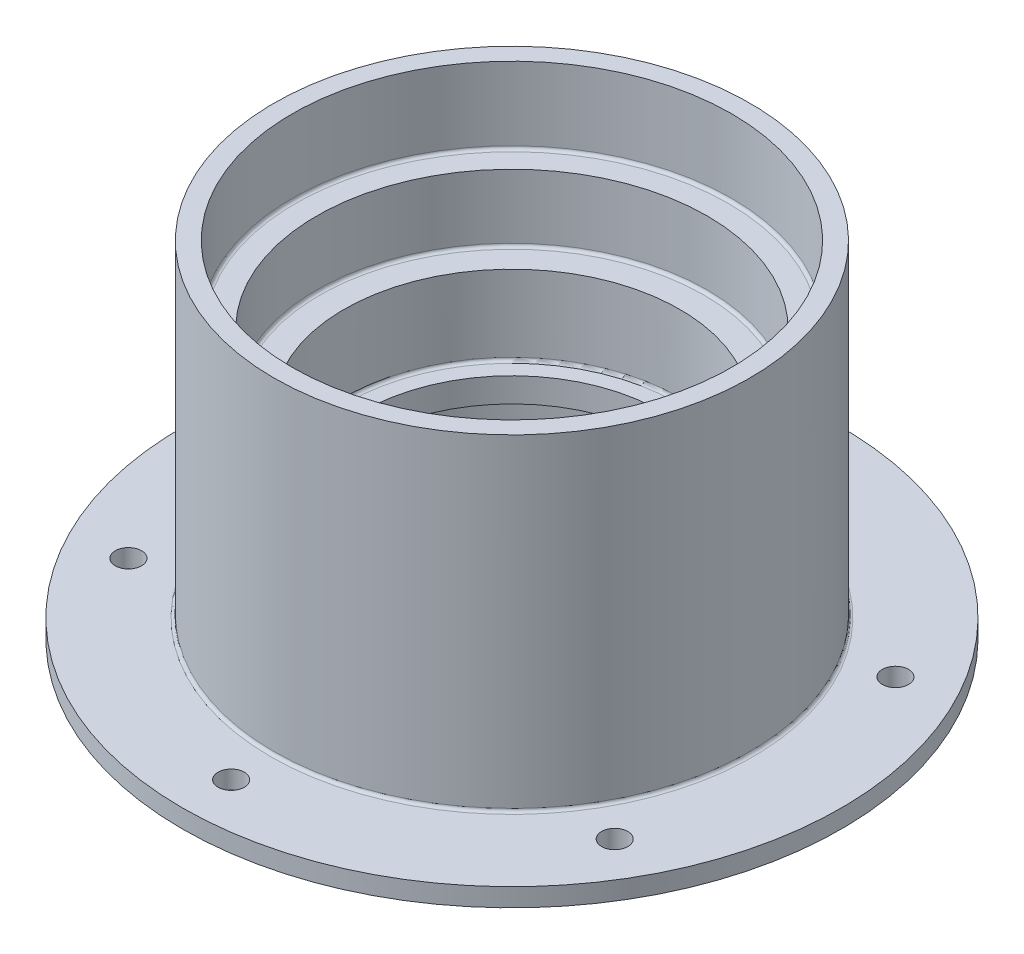
SolidWorks part; units mm, degrees
material "1060 Alloy"
ref_plane "Front" through (0, 0, 0) normal (0, 0, 1) x (1, 0, 0)
ref_plane "Top" through (0, 0, 0) normal (0, 1, 0) x (1, 0, 0)
ref_plane "Right" through (0, 0, 0) normal (1, 0, 0) x (0, 0, -1)
sketch "Sketch1" plane through (0, 0, 0) normal (0, 0, 1) x (1, 0, 0)
  line L0 (0, 0) -> (-39, 0)
  line L1 (-39, 0) -> (-39, -56.5)
  line L2 (-36, 0) -> (-36, -2)
  line L3 (-32, -15.5) -> (-32, -26.5)
  line L4 (-27.5, -26.5) -> (-27.5, -39.5)
  line L5 (-24.5, -39.5) -> (-24.5, -43.5)
  line L6 (-36, -3) -> (-37, -3)
  line L7 (-36, -15.5) -> (-32, -15.5)
  line L8 (-32, -26.5) -> (-27.5, -26.5)
  line L9 (-27.5, -39.5) -> (-24.5, -39.5)
  line L10 (-24.5, -43.5) -> (-32, -43.5)
  line L11 (-32, -59.5) -> (-54, -59.5)
  line L12 (-54, -59.5) -> (-54, -56.5)
  line L13 (-54, -56.5) -> (-39, -56.5)
  line L14 (0, 0) -> (0, -7.967)
  line L15 (-27.5, 0) -> (-27.5, -59.5) construction
  line L16 (-24.5, 0) -> (-24.5, -59.5) construction
  line L17 (-32, 0) -> (-32, -59.5) construction
  line L18 (-32, -43.5) -> (-32, -59.5)
  line L19 (-36, 0) -> (-36, -59.5) construction
  line L20 (-39, 0) -> (-39, -59.5) construction
  line L21 (-37, -3) -> (-37, -2)
  line L22 (-37, -2) -> (-36, -2)
  line L23 (-36, -3) -> (-36, -15.5)
  line L24 (-36, -0.5) -> (-39, -0.5)
  line L25 (-37, -3) -> (-39, -3)
  dimension "D2" = 3
  dimension "D3" = 4
  dimension "D4" = 4.5
  dimension "D5" = 3
  dimension "D6" = 3
  dimension "D7" = 12.5
  dimension "D8" = 11
  dimension "D9" = 13
  dimension "D10" = 4
  dimension "D11" = 16
  dimension "D12" = 3
  dimension "D13" = 15
  dimension "D14" = 1
  dimension "D15" = 1
  dimension "D16" = 0.5
  dimension "D17" = 39
  dimension "D18" = 32
  dimension "D19" = 27.5
  dimension "D20" = 24.5
revolve "Revolve1" add sketch "Sketch1" angle 360 about L14 region at (-35.5337, -36.9152, 0)
hole_wizard "M4 Clearance Hole1" positions "Sketch3" profile "Sketch2" hole size "M4" standard "ISO"
sketch "Sketch3" plane through (0, -56.5, 0) normal (0, 1, 0) x (1, 0, 0)
  point P65 (0, 46)
  point P73 (39.8372, 23)
  point P74 (39.8372, -23)
  point P75 (0, -46)
  point P76 (-39.8372, -23)
  point P77 (-39.8372, 23)
  dimension "D1" = 46
sketch "Sketch2" plane through (0, -56.5, -46) normal (1, 0, 0) x (0, 0, 1)
  line L0 (0, 0) -> (0, 101.2919)
  line L1 (0, 101.2919) -> (2.15, 100)
  line L2 (2.15, 100) -> (2.15, 0)
  line L5 (2.15, 0) -> (0, 0)
  line L10 (0, 101.2919) -> (-2.15, 100) construction
  line L11 (0, -6.35) -> (0, 107.95) construction
  dimension "Hole Dia." = 4.3
  dimension "Hole Depth" = 100
  dimension "Drill Angle" = 118
ref_plane "Plane1" [suppressed] through (0, -11, 0) normal (0, 1, 0) x (1, 0, 0)
sketch "Sketch5" [suppressed] plane through (0, -11, 0) normal (0, 1, 0) x (1, 0, 0)
  line L0 (31, 0) -> (31, 26.0103)
  line L3 (20, 32.1714) -> (20, 23.5698)
  line L4 (42, 32.1714) -> (42, 23.5698)
  circle A0 centre (31, 0) radius 26.0103
  circle A1 centre (31, 0) radius 34
  point P8 (31, 0)
  point P10 (31, 0)
  dimension "D1" = 11
  dimension "D2" = 11
sketch "Sketch6" plane through (0, -56.5, 0) normal (0, -1, 0) x (1, 0, 0)
  line L1 (-15.1843, 11) -> (-37.4166, 11)
  line L2 (-15.1843, -11) -> (-37.4166, -11)
  arc A0 (-28.4473, -11) -> (-28.4473, 11) centre (0, 0) ccw
  circle A1 centre (0, 0) radius 18.75
  circle A2 centre (0, 0) radius 39
  circle M17 centre (0, 0) radius 39
extrude "Cut-Extrude1" cut sketch "Sketch6" against normal blind 10 contours A1 L2 M17 | L1 A1 M17 region at (-28.0227, -56.5, 0)
fillet "Fillet1" radius 0.5 5 edges at (0, -43.5, 32) (0, -26.5, 32) (39, -56.5, 0) (0, -39.5, 27.5) (0, -15.5, 36)
